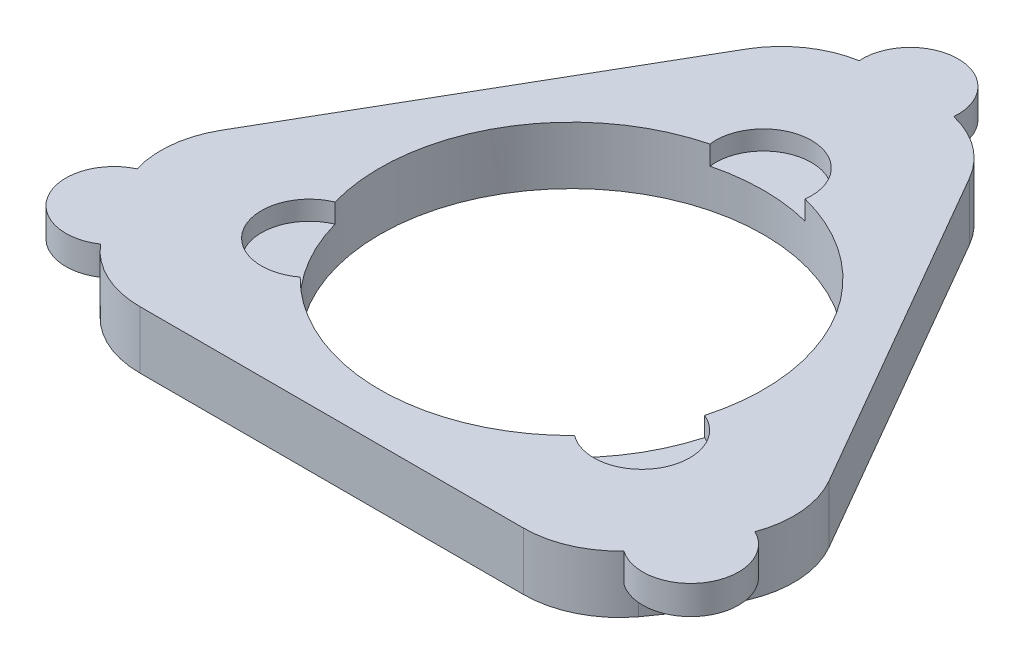
SolidWorks part; units mm, degrees
ref_plane "Спереди" through (0, 0, 0) normal (0, 0, 1) x (1, 0, 0)
ref_plane "Сверху" through (0, 0, 0) normal (0, 1, 0) x (1, 0, 0)
ref_plane "Справа" through (0, 0, 0) normal (1, 0, 0) x (0, 0, -1)
sketch "Sketch1" plane through (0, 0, 0) normal (0, 1, 0) x (1, 0, 0)
  circle A0 centre (0, 0) radius 20
  dimension "D1" = 40
extrude "Boss-Extrude1" add sketch "Sketch1" along normal blind 3.5
sketch "Sketch2" plane through (0, 0, 0) normal (0, 1, 0) x (1, 0, 0)
  circle A0 centre (0, 0) radius 35
  circle A1 centre (0, 0) radius 20
  circle A2 centre (0, 0) radius 28.3 construction
  circle A3 centre (0, 28.3) radius 2.8
  circle A4 centre (24.5085, -14.15) radius 2.8
  circle A5 centre (-24.5085, -14.15) radius 2.8
  point P7 (0, 0)
  point P8 (0, 0)
  point P9 (0, 0)
  point P14 (0, 0)
  point P16 (0, 0)
  dimension "D2" = 56.6
  dimension "D3" = 40
  dimension "D4" = 70
  dimension "D1" = 3
extrude "Boss-Extrude2" add sketch "Sketch2" along normal blind 6
sketch "Sketch4" plane through (0, 0, 0) normal (0, -1, 0) x (1, 0, 0)
  circle A0 centre (-24.5085, 14.15) radius 2.9
  circle A1 centre (24.5085, 14.15) radius 2.9
  circle A2 centre (0, -28.3) radius 2.9
  point P3 (0, 0)
  point P4 (0, 0)
  point P9 (0, 0)
  dimension "D1" = 3
extrude "Boss-Extrude3" add sketch "Sketch4" along normal blind 2 and the other way up to surface (6 mm away) other way up to face at (24.5085, 6, 16.95)
sketch "Sketch5" plane through (0, 6, 0) normal (0, 1, 0) x (1, 0, 0)
  circle A0 centre (-30.4536, -17.2504) radius 5
  circle A1 centre (0, 0) radius 35 construction
  circle A2 centre (0.2875, 34.9988) radius 5
  circle A3 centre (30.1661, -17.7484) radius 5
  point P10 (0, 0)
  dimension "D1" = 3
extrude "Boss-Extrude4" add sketch "Sketch5" against normal blind 3
sketch "Sketch3" plane through (0, 3.5, 0) normal (0, 1, 0) x (1, 0, 0)
  circle A0 centre (0, 0) radius 20
  dimension "D1" = 40
extrude "Cut-Extrude1" cut sketch "Sketch3" against normal blind 10
sketch "Sketch12" plane through (0, 6, 0) normal (0, 1, 0) x (1, 0, 0)
  line L1 (0, 50) -> (-43.3013, -25)
  line L2 (-43.3013, -25) -> (43.3013, -25)
  line L3 (43.3013, -25) -> (0, 50)
  circle A0 centre (0, 0) radius 25 construction
  circle A1 centre (0, 0) radius 72.1359
extrude "Cut-Extrude2" cut sketch "Sketch12" against normal blind 22
fillet "Fillet1" radius 10 6 edges at (-24.4949, 3, 25) (-33.8981, 3, 8.7132) (24.4949, 3, 25) (33.8981, 3, 8.7132) (9.4032, 3, -33.7132) (-9.4032, 3, -33.7132)
sketch "Sketch15" plane through (0, 6, 0) normal (0, 1, 0) x (1, 0, 0)
  circle A0 centre (0, 20) radius 5
  circle A1 centre (0, 0) radius 20 construction
  circle A2 centre (0, 0) radius 20
  circle A3 centre (17.3205, -10) radius 5
  circle A4 centre (-17.3205, -10) radius 5
  point P15 (0, 0)
  circle M8 centre (0, 0) radius 20
  dimension "D1" = 3
extrude "Cut-Extrude4" cut sketch "Sketch15" against normal blind 2 contours A0 M8 | A2 A4 | A2 A3 region at (0, 6, -22.0055) region at (-19.0573, 6, 11.0028) region at (19.0573, 6, 11.0028)
